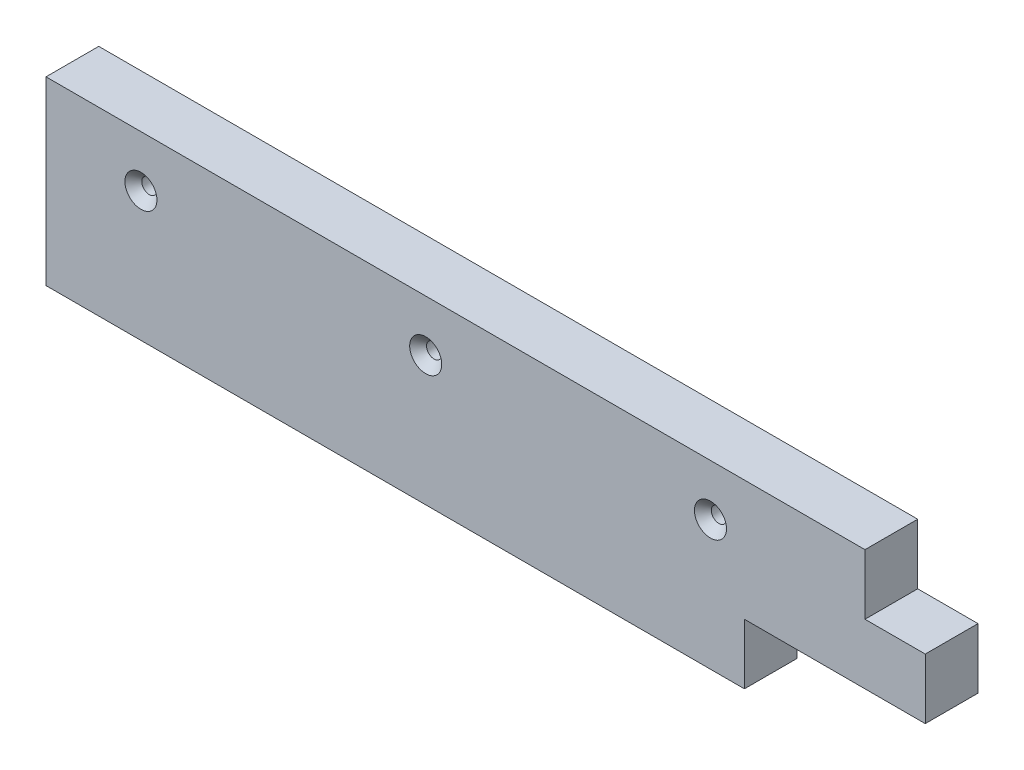
SolidWorks part; units mm, degrees
ref_plane "Front Plane" through (0, 0, 0) normal (0, 0, 1) x (1, 0, 0)
ref_plane "Top Plane" through (0, 0, 0) normal (0, 1, 0) x (1, 0, 0)
ref_plane "Right Plane" through (0, 0, 0) normal (1, 0, 0) x (0, 0, -1)
sketch "Sketch1" plane through (0, 0, 0) normal (0, 1, 0) x (1, 0, 0)
  line L1 (-185.2521, -11.1125) -> (185.2521, -11.1125)
  line L2 (-185.2521, -11.1125) -> (-185.2521, 11.1125)
  line L3 (-185.2521, 11.1125) -> (185.2521, 11.1125)
  line L4 (185.2521, -11.1125) -> (185.2521, 11.1125)
  line L5 (-185.2521, -11.1125) -> (185.2521, 11.1125) construction
  line L6 (-185.2521, 11.1125) -> (185.2521, -11.1125) construction
  point P0 (0, 0)
extrude "Boss-Extrude1" add sketch "Sketch1" along normal mid plane 76.2 contours L1 L4 L3 L2
sketch "Sketch3" plane through (0, 0, 11.1125) normal (0, 0, 1) x (1, 0, 0)
  line L1 (185.2521, 38.1) -> (159.8521, 38.1)
  line L2 (185.2521, 38.1) -> (185.2521, 12.7)
  line L3 (185.2521, 12.7) -> (159.8521, 12.7)
  line L4 (159.8521, 38.1) -> (159.8521, 12.7)
  line L5 (109.0521, -12.7) -> (185.2521, -12.7)
  line L6 (109.0521, -12.7) -> (109.0521, -38.1)
  line L7 (109.0521, -38.1) -> (185.2521, -38.1)
  line L8 (185.2521, -12.7) -> (185.2521, -38.1)
  dimension "D1" = 76.2
  dimension "D2" = 25.4
  dimension "D3" = 25.4
hole_wizard "CSK for M6 Hex Socket Countersunk Head Screw6" positions "Sketch21" profile "Sketch20" countersink size "M6" standard "Lanco STD" end condition through all
sketch "Sketch21" plane through (0, 0, 11.1125) normal (0, 0, 1) x (1, 0, 0)
  point P0 (-145.2521, 16.5075)
  point P8 (-25.2521, 16.5075)
  point P11 (94.7479, 16.5075)
sketch "Sketch20" plane through (-145.2521, 16.5075, 11.1125) normal (1, 0, 0) x (0, -1, 0)
  line L0 (0, 0) -> (0, 22.225)
  line L1 (0, 22.225) -> (3.2, 22.225)
  line L2 (3.2, 22.225) -> (3.2, 3.55)
  line L3 (3.2, 3.55) -> (6.75, 0)
  line L5 (6.75, 0) -> (0, 0)
  line L6 (-3.2, 3.55) -> (-6.75, 0) construction
  line L11 (0, -6.35) -> (0, 107.95) construction
  dimension "Thru Hole Dia." = 6.4
  dimension "Thru Hole Depth" = 22.225
  dimension "Near C'Sink Dia." = 13.5
  dimension "Near C'Sink Angle" = 90
extrude "Cut-Extrude1" cut sketch "Sketch3" against normal through all
